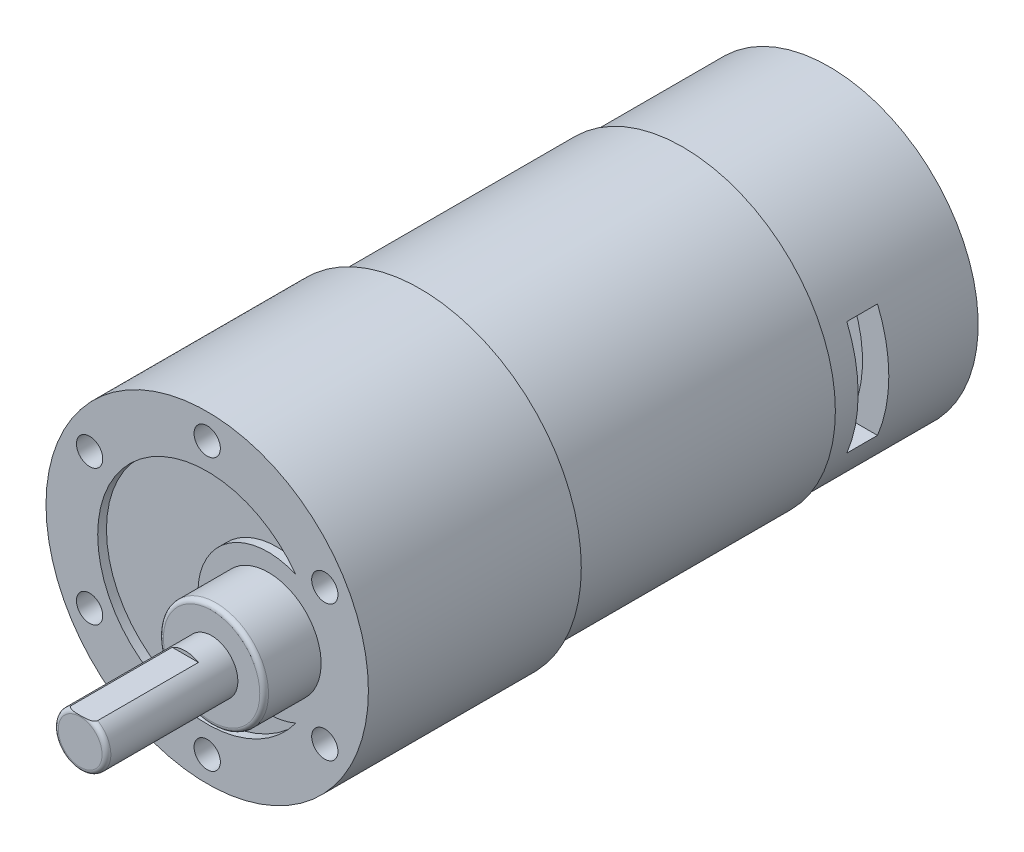
SolidWorks part; units mm, degrees
ref_plane "Front Plane" through (0, 0, 0) normal (0, 0, 1) x (1, 0, 0)
ref_plane "Top Plane" through (0, 0, 0) normal (0, 1, 0) x (1, 0, 0)
ref_plane "Right Plane" through (0, 0, 0) normal (1, 0, 0) x (0, 0, -1)
sketch "Sketch1" plane through (0, 0, 0) normal (0, 0, 1) x (1, 0, 0)
  circle A0 centre (0, 0) radius 18.4
  dimension "D1" = 36.8
extrude "Boss-Extrude1" add sketch "Sketch1" along normal blind 24.3
sketch "Sketch2" plane through (0, 0, 0) normal (0, 0, -1) x (-1, 0, 0)
  circle A0 centre (0, 0) radius 17.4
  dimension "D1" = 34.8
extrude "Boss-Extrude2" add sketch "Sketch2" along normal blind 30
sketch "Sketch3" plane through (0, 0, 24.3) normal (0, 0, 1) x (1, 0, 0)
  circle A0 centre (7, 0) radius 6
  dimension "D1" = 12
  dimension "D2" = 7
extrude "Boss-Extrude3" add sketch "Sketch3" along normal blind 6.5
fillet "Fillet1" radius 0.5 1 edges at (13, 0, 30.8)
sketch "Sketch4" plane through (0, 0, 30.8) normal (0, 0, 1) x (1, 0, 0)
  line L0 (7, -6.8172) -> (7, 7.1125) construction
  circle A0 centre (7, 0) radius 3
  dimension "D1" = 6
extrude "Boss-Extrude4" add sketch "Sketch4" along normal blind 15
sketch "Sketch5" plane through (0, 0, 45.8) normal (0, 0, 1) x (1, 0, 0)
  line L0 (5.5033, 2.6) -> (8.4967, 2.6)
  line L1 (7, -3) -> (9.3109, -3) construction
  circle A0 centre (7, 0) radius 3 construction
  circle A1 centre (7, 0) radius 3 construction
  arc A2 (8.4967, 2.6) -> (5.5033, 2.6) centre (7, 0) ccw
  dimension "D1" = 5.6
extrude "Cut-Extrude1" cut sketch "Sketch5" against normal blind 12
hole_wizard "Ø3.0 (3) Diameter Hole1" positions "Sketch7" profile "Sketch6" hole size "Ø3.0" standard "Ansi Metric"
sketch "Sketch7" plane through (0, 0, 24.3) normal (0, 0, 1) x (1, 0, 0)
  point P0 (-13.4234, 7.75)
  point P1 (-13.4234, -7.75)
  point P3 (0, -15.5)
  point P5 (13.4234, 7.75)
  point P7 (0, 15.5)
  point P22 (13.4234, -7.75)
  dimension "D1" = 15.5
  dimension "D2" = 15.5
  dimension "D3" = 15.5
  dimension "D4" = 15.5
  dimension "D5" = 15.5
  dimension "D6" = 15.5
  dimension "D7" = 15.5
  dimension "D8" = 15.5
  dimension "D9" = 15.5
  dimension "D10" = 15.5
sketch "Sketch6" plane through (-13.4234, 7.75, 24.3) normal (1, 0, 0) x (0, -1, 0)
  line L0 (0, 0) -> (0, 3.9013)
  line L1 (0, 3.9013) -> (1.5, 3)
  line L2 (1.5, 3) -> (1.5, 0)
  line L5 (1.5, 0) -> (0, 0)
  line L10 (0, 3.9013) -> (-1.5, 3) construction
  line L11 (0, -6.35) -> (0, 107.95) construction
  dimension "Hole Dia." = 3
  dimension "Hole Depth" = 3
  dimension "Drill Angle" = 118
sketch "Sketch8" plane through (0, 0, 24.3) normal (0, 0, 1) x (1, 0, 0)
  line L0 (-0.5907, 0) -> (14.4711, 0) construction
  line L1 (7, 7.3586) -> (7, -7.457) construction
  arc A0 (10.1162, 7.3426) -> (10.1162, -7.3426) centre (0, 0) ccw
  arc A1 (10.1162, 7.3426) -> (10.1162, -7.3426) centre (6.9402, 0) ccw
  dimension "D1" = 25
  dimension "D2" = 16
extrude "Cut-Extrude2" cut sketch "Sketch8" against normal blind 1
sketch "Sketch9" plane through (0, 0, -30) normal (0, 0, -1) x (-1, 0, 0)
  circle A0 centre (0, 0) radius 4
  dimension "D1" = 8
extrude "Boss-Extrude5" add sketch "Sketch9" along normal blind 1
fillet "Fillet2" radius 0.5 1 edges at (-4, 0, -31)
ref_plane "Plane1" through (0, 0, -33) normal (0, 0, -1) x (-1, 0, 0)
sketch "Sketch10" plane through (0, 0, -33) normal (0, 0, -1) x (-1, 0, 0)
  circle A0 centre (0, 0) radius 14
  dimension "D1" = 28
extrude "Boss-Extrude6" add sketch "Sketch10" along normal blind 1.5 separate body
sketch "Sketch11" plane through (0, 0, -30) normal (0, 0, -1) x (-1, 0, 0)
  line L0 (0, 11.55) -> (0, 12.55) construction
  line L1 (-1.75, 12.55) -> (1.75, 12.55)
  line L2 (-1.75, 12.55) -> (-1.75, 11.55)
  line L3 (-1.75, 11.55) -> (1.75, 11.55)
  line L4 (1.75, 12.55) -> (1.75, 11.55)
  line L5 (-1.75, 12.05) -> (1.75, 12.05) construction
  line L6 (-3.5, 0) -> (3.5, 0) construction
  line L7 (1.75, -12.55) -> (1.75, -11.55)
  line L8 (-1.75, -12.55) -> (-1.75, -11.55)
  line L9 (-1.75, -12.55) -> (1.75, -12.55)
  line L10 (-1.75, -11.55) -> (1.75, -11.55)
  circle A0 centre (0, 0) radius 3.5 construction
  dimension "D1" = 3.5
  dimension "D2" = 1
  dimension "D3" = 12.05
extrude "Boss-Extrude7" add sketch "Sketch11" along normal blind 5.6
fillet "Fillet3" radius 0.5 4 edges at (-1.75, -12.05, -35.6) (1.75, -12.05, -35.6) (-1.75, 12.05, -35.6) (1.75, 12.05, -35.6)
ref_plane "Plane2" through (0, 0, -36.5) normal (0, 0, -1) x (-1, 0, 0)
sketch "Sketch13" plane through (0, 0, -36.5) normal (0, 0, -1) x (-1, 0, 0)
  circle A0 centre (0, 0) radius 9
  dimension "D1" = 18
extrude "Boss-Extrude8" add sketch "Sketch13" along normal blind 3 separate body
sketch "Sketch14" plane through (0, 0, -31) normal (0, 0, -1) x (-1, 0, 0)
  circle A0 centre (0, 0) radius 1.5
  dimension "D1" = 3
extrude "Boss-Extrude9" add sketch "Sketch14" along normal blind 8.55
fillet "Fillet4" radius 0.5 1 edges at (7, -3, 45.8)
sketch "Sketch15" plane through (0, 0, 0) normal (0, 1, 0) x (1, 0, 0)
  line L0 (-17, 30) -> (-17, 46.7)
  line L1 (-17, 46.7) -> (-14, 46.7)
  line L2 (-14, 46.7) -> (-14, 30)
  line L3 (17.4, 30) -> (-17.4, 30) construction
  line L4 (-14, 30) -> (-17, 30)
  line L6 (-18.4, -24.3) -> (18.4, -24.3) construction
  line L7 (0, 30) -> (0, 0) construction
  dimension "D1" = 71
  dimension "D2" = 3
  dimension "D3" = 17
revolve "Revolve1" add sketch "Sketch15" angle 360 about axis through (0, 0, -30) along (0, 0, 1)
sketch "Sketch16" plane through (0, 0, -46.7) normal (0, 0, -1) x (-1, 0, 0)
  circle A0 centre (0, 0) radius 14 construction
  circle A1 centre (0, 0) radius 14
extrude "Boss-Extrude10" add sketch "Sketch16" against normal blind 1
sketch "Sketch17" plane through (0, 0, 0) normal (1, 0, 0) x (0, 0, -1)
  line L1 (33, 6.5) -> (36.5, 6.5)
  line L2 (33, 6.5) -> (33, -6.5)
  line L3 (33, -6.5) -> (36.5, -6.5)
  line L4 (36.5, 6.5) -> (36.5, -6.5)
  line L7 (30, -17.4) -> (30, 17.4) construction
  dimension "D1" = 3
  dimension "D2" = 3.5
  dimension "D3" = 13
extrude "Cut-Extrude3" cut sketch "Sketch17" along normal through all from offset 12
